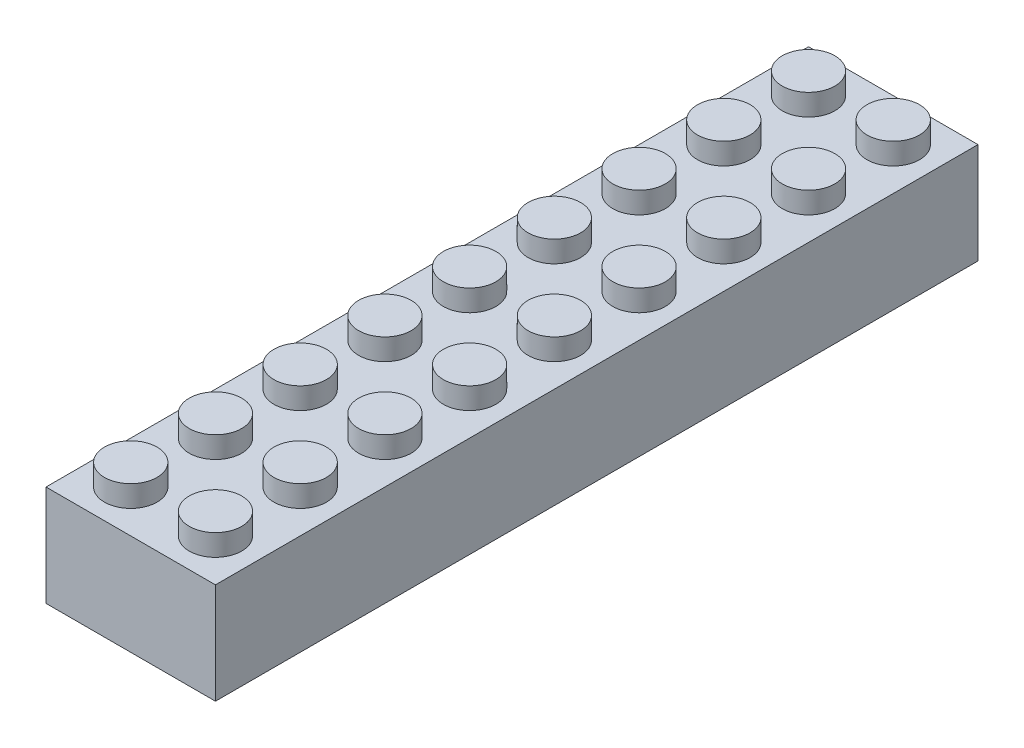
SolidWorks part; units mm, degrees
ref_plane "Front Plane" through (0, 0, 0) normal (0, 0, 1) x (1, 0, 0)
ref_plane "Top Plane" through (0, 0, 0) normal (0, 1, 0) x (1, 0, 0)
ref_plane "Right Plane" through (0, 0, 0) normal (1, 0, 0) x (0, 0, -1)
sketch "stencil" plane through (0, 0, 0) normal (0, 1, 0) x (1, 0, 0)
  line L2 (7.9, 71.1) -> (7.9, 0) construction
  line L29 (14.35, 1.45) -> (1.45, 1.45)
  line L30 (15.75, 71.05) -> (0.05, 71.05)
  line L32 (15.75, 71.05) -> (15.75, 0.05)
  line L34 (15.75, 0.05) -> (0.05, 0.05)
  line L36 (0.05, 71.05) -> (0.05, 0.05)
  line L37 (7.9, 0.05) -> (7.9, 71.05) construction
  line L38 (15.75, 35.55) -> (0.05, 35.55) construction
  line L39 (1.45, 69.65) -> (1.45, 1.45)
  line L40 (14.35, 69.65) -> (1.45, 69.65)
  line L41 (14.35, 69.65) -> (14.35, 1.45)
  circle A40 centre (3.95, 3.95) radius 2.45
  circle A41 centre (7.9, 7.9) radius 3.2
  circle A42 centre (3.95, 11.85) radius 2.45
  circle A43 centre (3.95, 19.75) radius 2.45
  circle A44 centre (3.95, 27.65) radius 2.45
  circle A45 centre (7.9, 15.8) radius 3.2
  circle A46 centre (7.9, 23.7) radius 3.2
  circle A47 centre (7.9, 31.6) radius 3.2
  circle A48 centre (3.95, 35.55) radius 2.45
  circle A49 centre (3.95, 43.45) radius 2.45
  circle A50 centre (3.95, 51.35) radius 2.45
  circle A51 centre (7.9, 39.5) radius 3.2
  circle A52 centre (7.9, 47.4) radius 3.2
  circle A53 centre (3.95, 59.25) radius 2.45
  circle A54 centre (3.95, 67.15) radius 2.45
  circle A55 centre (7.9, 55.3) radius 3.2
  circle A56 centre (7.9, 63.2) radius 3.2
  circle A57 centre (7.9, 7.9) radius 2.4
  circle A58 centre (7.9, 15.8) radius 2.4
  circle A59 centre (7.9, 23.7) radius 2.4
  circle A60 centre (7.9, 31.6) radius 2.4
  circle A61 centre (7.9, 39.5) radius 2.4
  circle A62 centre (7.9, 47.4) radius 2.4
  circle A63 centre (7.9, 55.3) radius 2.4
  circle A64 centre (7.9, 63.2) radius 2.4
  circle A65 centre (11.85, 11.85) radius 2.45
  circle A66 centre (11.85, 19.75) radius 2.45
  circle A67 centre (11.85, 27.65) radius 2.45
  circle A68 centre (11.85, 35.55) radius 2.45
  circle A69 centre (11.85, 43.45) radius 2.45
  circle A70 centre (11.85, 51.35) radius 2.45
  circle A71 centre (11.85, 59.25) radius 2.45
  circle A72 centre (11.85, 67.15) radius 2.45
  circle A73 centre (11.85, 3.95) radius 2.45
  point P1 (0, 0)
  point P6 (3.95, -15.8)
  point P9 (7.9, -15.8)
  point P10 (7.9, -11.85)
  point P13 (3.95, -7.9)
  point P15 (7.9, -7.9)
  point P17 (7.9, -3.95)
  point P18 (3.95, 0)
  point P21 (7.9, 0)
  point P25 (7.9, 3.95)
  point P27 (3.95, 7.9)
  point P28 (7.9, 7.9)
  point P29 (0, -11.85)
  point P30 (0, -7.9)
  point P31 (0, 3.95)
  point P34 (0, -3.95)
  point P35 (3.95, 0)
  point P36 (0, 15.8)
  point P37 (0, 23.7)
  point P38 (7.9, 23.7)
  point P39 (15.8, 23.7)
  point P40 (15.8, 15.8)
  point P41 (15.8, 7.9)
  point P43 (7.9, 0)
  point P48 (11.85, 0)
  point P49 (15.8, 0)
  point P50 (3.95, 3.95)
  point P51 (7.9, 3.95)
  point P52 (11.85, 3.95)
  point P53 (15.8, 3.95)
  point P54 (3.95, 7.9)
  point P55 (7.9, 7.9)
  point P56 (11.85, 7.9)
  point P57 (15.8, 7.9)
  point P58 (3.95, 11.85)
  point P59 (7.9, 11.85)
  point P60 (11.85, 11.85)
  point P61 (15.8, 11.85)
  point P63 (3.95, 15.8)
  point P64 (7.9, 15.8)
  point P65 (11.85, 15.8)
  point P66 (15.8, 15.8)
  point P67 (3.95, 19.75)
  point P68 (7.9, 19.75)
  point P69 (11.85, 19.75)
  point P70 (15.8, 19.75)
  point P71 (3.95, 23.7)
  point P72 (7.9, 23.7)
  point P73 (11.85, 23.7)
  point P75 (15.8, 23.7)
  point P77 (3.95, 27.65)
  point P79 (7.9, 27.65)
  point P81 (11.85, 27.65)
  point P83 (15.8, 27.65)
  point P85 (3.95, 31.6)
  point P87 (7.9, 31.6)
  point P88 (11.85, 31.6)
  point P89 (15.8, 31.6)
  point P90 (0, 3.95)
  point P91 (0, 7.9)
  point P92 (0, 11.85)
  point P93 (0, 15.8)
  point P94 (0, 19.75)
  point P95 (0, 23.7)
  point P96 (0, 27.65)
  point P97 (0, 31.6)
  point P113 (0, 35.55)
  point P114 (3.95, 35.55)
  point P115 (7.9, 35.55)
  point P116 (11.85, 35.55)
  point P117 (15.8, 35.55)
  point P118 (0, 39.5)
  point P119 (3.95, 39.5)
  point P120 (7.9, 39.5)
  point P121 (11.85, 39.5)
  point P122 (15.8, 39.5)
  point P124 (0, 43.45)
  point P125 (3.95, 43.45)
  point P126 (7.9, 43.45)
  point P127 (11.85, 43.45)
  point P128 (15.8, 43.45)
  point P129 (0, 47.4)
  point P130 (3.95, 47.4)
  point P131 (7.9, 47.4)
  point P132 (11.85, 47.4)
  point P133 (15.8, 47.4)
  point P135 (0, 51.35)
  point P136 (3.95, 51.35)
  point P137 (7.9, 51.35)
  point P138 (11.85, 51.35)
  point P139 (15.8, 51.35)
  point P140 (0, 55.3)
  point P141 (3.95, 55.3)
  point P142 (7.9, 55.3)
  point P143 (11.85, 55.3)
  point P144 (15.8, 55.3)
  point P145 (0, 59.25)
  point P146 (3.95, 59.25)
  point P147 (7.9, 59.25)
  point P148 (11.85, 59.25)
  point P149 (15.8, 59.25)
  point P150 (0, 63.2)
  point P151 (3.95, 63.2)
  point P152 (7.9, 63.2)
  point P153 (11.85, 63.2)
  point P154 (15.8, 63.2)
  point P165 (0, 67.15)
  point P166 (3.95, 67.15)
  point P167 (7.9, 67.15)
  point P168 (11.85, 67.15)
  point P169 (15.8, 67.15)
  point P170 (0, 71.1)
  point P171 (3.95, 71.1)
  point P172 (7.9, 71.1)
  point P173 (11.85, 71.1)
  point P174 (15.8, 71.1)
  point P182 (7.9, 35.55)
  dimension "D8" = 4.9
  dimension "D9" = 6.4
  dimension "D3" = 3.95
  dimension "D4" = 3.95
  dimension "D5" = 15.7
  dimension "D6" = 71
  dimension "D7" = 0.8
  dimension "D10" = 1.4
  dimension "D1" = 5
  dimension "D2" = 19
sketch "Sketch1" plane through (0, 0, 0) normal (0, 1, 0) x (1, 0, 0)
  line L1 (15.8, 71.1) -> (0, 71.1)
  line L2 (15.8, 71.1) -> (15.8, 0)
  line L3 (15.8, 0) -> (0, 0)
  line L4 (0, 71.1) -> (0, 0)
  line L5 (7.9, 0) -> (7.9, 71.1) construction
  line L6 (15.8, 35.55) -> (0, 35.55) construction
  point P0 (7.9, 35.55)
extrude "Boss-Extrude1" add sketch "Sketch1" along normal mid plane 9.4
sketch "Sketch2" plane through (0, 4.7, 0) normal (0, 1, 0) x (1, 0, 0)
  line L0 (0, 71.1) -> (0, 0) construction
  circle A0 centre (3.95, 3.95) radius 2.45
  circle A1 centre (11.85, 3.95) radius 2.45
  circle A2 centre (11.85, 11.85) radius 2.45
  circle A3 centre (3.95, 11.85) radius 2.45
  circle A4 centre (3.95, 19.75) radius 2.45
  circle A5 centre (3.95, 27.65) radius 2.45
  circle A6 centre (11.85, 27.65) radius 2.45
  circle A7 centre (11.85, 35.55) radius 2.45
  circle A8 centre (3.95, 35.55) radius 2.45
  circle A9 centre (3.95, 43.45) radius 2.45
  circle A10 centre (11.85, 43.45) radius 2.45
  circle A11 centre (3.95, 51.35) radius 2.45
  circle A12 centre (11.85, 51.35) radius 2.45
  circle A13 centre (3.95, 59.25) radius 2.45
  circle A14 centre (11.85, 59.25) radius 2.45
  circle A15 centre (3.95, 67.15) radius 2.45
  circle A16 centre (11.85, 67.15) radius 2.45
  circle A17 centre (3.95, 3.95) radius 2.45 construction
  circle A18 centre (11.85, 19.75) radius 2.45
  circle A19 centre (11.85, 19.75) radius 2.45 construction
extrude "Boss-Extrude2" add sketch "Sketch2" along normal blind 2
sketch "Sketch3" plane through (0, -4.7, 0) normal (0, -1, 0) x (1, 0, 0)
  line L1 (14.35, -1.45) -> (1.45, -1.45)
  line L2 (14.35, -1.45) -> (14.35, -69.65)
  line L3 (14.35, -69.65) -> (1.45, -69.65)
  line L4 (1.45, -1.45) -> (1.45, -69.65)
  line L5 (7.9, -69.65) -> (7.9, -1.45) construction
  line L6 (14.35, -35.55) -> (1.45, -35.55) construction
  point P0 (7.9, -35.55)
extrude "Cut-Extrude1" cut sketch "Sketch3" against normal blind 4
sketch "Sketch4" plane through (0, -0.7, 0) normal (0, -1, 0) x (1, 0, 0)
  circle A0 centre (7.9, -63.2) radius 3.2
  circle A1 centre (7.9, -55.3) radius 3.2
  circle A2 centre (7.9, -47.4) radius 3.2
  circle A3 centre (7.9, -39.5) radius 3.2
  circle A4 centre (7.9, -31.6) radius 3.2
  circle A5 centre (7.9, -23.7) radius 3.2
  circle A6 centre (7.9, -15.8) radius 3.2
  circle A7 centre (7.9, -7.9) radius 3.2
  circle A8 centre (7.9, -7.9) radius 2.4
  circle A10 centre (7.9, -15.8) radius 2.4
  circle A11 centre (7.9, -23.7) radius 2.4
  circle A12 centre (7.9, -31.6) radius 2.4
  circle A13 centre (7.9, -39.5) radius 2.4
  circle A14 centre (7.9, -47.4) radius 2.4
  circle A15 centre (7.9, -55.3) radius 2.4
  circle A16 centre (7.9, -63.2) radius 2.4
  circle A17 centre (7.9, -63.2) radius 2.4 construction
  circle A18 centre (7.9, -63.2) radius 3.2 construction
extrude "Boss-Extrude3" add sketch "Sketch4" along normal up to surface (4 mm away) up to face at (7.9, -4.7, -35.55)
equation "\"t\"= 0.10'tolerance"
equation "\"D5@stencil\"=15.80-\"t\""
equation "\"D10@stencil\"=1.5-\"t\""
equation "\"D6@stencil\"=71.10mm-\"t\""
equation "\"D1@Boss-Extrude1\"=9.50mm-\"t\""
equation "\"D9@stencil\"=6.5-\"t\""
